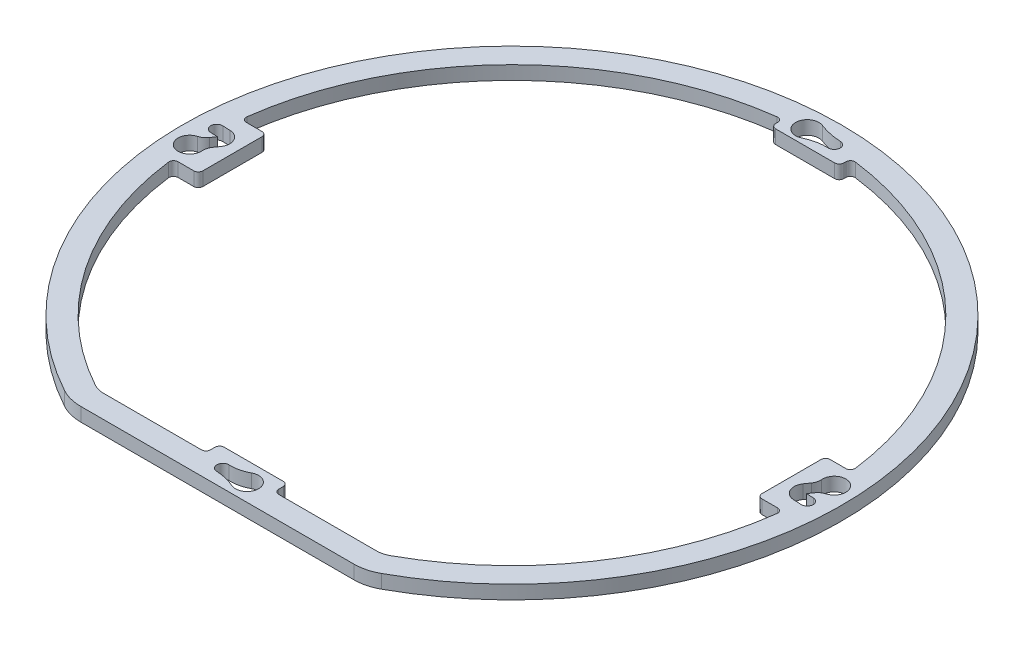
SolidWorks part; units mm, degrees
material "ABS"
ref_plane "Front Plane" through (0, 0, 0) normal (0, 0, 1) x (1, 0, 0)
ref_plane "Top Plane" through (0, 0, 0) normal (0, 1, 0) x (1, 0, 0)
ref_plane "Right Plane" through (0, 0, 0) normal (1, 0, 0) x (0, 0, -1)
sketch "Sketch1" plane through (0, 0, 0) normal (0, 1, 0) x (1, 0, 0)
  line L0 (-30.03, -64.8129) -> (30.03, -64.8129)
  line L1 (0, -85) -> (0, 0) construction
  line L2 (0, -85) -> (32.4891, -64.8129) construction
  line L3 (-30.03, -59.8129) -> (30.03, -59.8129)
  arc A0 (34.8348, -63.5829) -> (-34.8348, -63.5829) centre (0, 0) ccw
  circle A1 centre (0, -85) radius 38.25 construction
  arc A2 (30.03, -64.8129) -> (34.8348, -63.5829) centre (30.03, -54.8129) ccw
  arc A3 (-30.03, -64.8129) -> (-34.8348, -63.5829) centre (-30.03, -54.8129) cw
  arc A4 (32.4324, -59.1979) -> (-32.4324, -59.1979) centre (0, 0) ccw
  arc A5 (-30.03, -59.8129) -> (-32.4324, -59.1979) centre (-30.03, -54.8129) cw
  arc A6 (30.03, -59.8129) -> (32.4324, -59.1979) centre (30.03, -54.8129) ccw
  dimension "D1" = 145
  dimension "D2" = 76.5
  dimension "D4" = 10
  dimension "D3" = 85
  dimension "D5" = 5
extrude "Boss-Extrude1" add sketch "Sketch1" along normal blind 3
sketch "Sketch2" plane through (0, 3, 0) normal (0, 1, 0) x (1, 0, 0)
  line L0 (-30.03, -59.8129) -> (30.03, -59.8129) construction
  line L1 (7.5, -59.8129) -> (-7.5, -59.8129)
  line L2 (7.5, -59.8129) -> (7.5, -56.8129)
  line L3 (7.5, -56.8129) -> (-7.5, -56.8129)
  line L4 (-7.5, -59.8129) -> (-7.5, -56.8129)
  line L5 (-30.03, -64.8129) -> (30.03, -64.8129) construction
  line L6 (-61.5, -7.5) -> (-67.5, -7.5)
  line L7 (-61.5, -7.5) -> (-61.5, 7.5)
  line L8 (-61.5, 7.5) -> (-67.5, 7.5)
  line L9 (-67.5, -7.5) -> (-67.5, 7.5)
  line L10 (61.5, -7.5) -> (67.5, -7.5)
  line L11 (61.5, -7.5) -> (61.5, 7.5)
  line L12 (61.5, 7.5) -> (67.5, 7.5)
  line L13 (67.5, -7.5) -> (67.5, 7.5)
  line L14 (7.5, 67.5) -> (-7.5, 67.5)
  line L15 (7.5, 67.5) -> (7.5, 64.5)
  line L16 (7.5, 64.5) -> (-7.5, 64.5)
  line L17 (-7.5, 67.5) -> (-7.5, 64.5)
  arc A0 (32.4324, -59.1979) -> (-32.4324, -59.1979) centre (0, 0) ccw construction
  point P17 (-67.5, 0)
  point P18 (67.5, 0)
  point P20 (0, -56.8129)
  point P26 (0, 67.5)
  dimension "D4" = 3
  dimension "D1" = 15
  dimension "D2" = 8
  dimension "D3" = 15
  dimension "D5" = 6
extrude "Boss-Extrude2" add sketch "Sketch2" against normal up to surface (3 mm away) up to face at (0, 0, 30.3285)
sketch "Sketch3" plane through (0, 3, 0) normal (0, 1, 0) x (1, 0, 0)
  line L0 (0, 0) -> (2.6608, -60.9419) construction
  line L1 (0, 0) -> (-2.6608, -60.9419) construction
  line L2 (0, 0) -> (0, -64.8129) construction
  line L3 (-30.03, -64.8129) -> (30.03, -64.8129) construction
  line L4 (0, 0) -> (0, 72.5) construction
  line L5 (0, 0) -> (2.9661, 67.9353) construction
  line L6 (0, 0) -> (-2.9661, 67.9353) construction
  arc A0 (1.6164, -63.2683) -> (1.438, -58.7042) centre (2.6608, -60.9419) ccw
  arc A1 (-2.6041, -59.6432) -> (-2.7175, -62.2407) centre (-2.6608, -60.9419) ccw
  arc A2 (-2.6041, -59.6432) -> (1.438, -58.7042) centre (-2.2671, -51.9241) ccw
  arc A3 (1.6164, -63.2683) -> (-2.7175, -62.2407) centre (-3.2341, -74.0728) ccw
  arc A4 (34.8348, -63.5829) -> (-34.8348, -63.5829) centre (0, 0) ccw construction
  arc A5 (2.9094, 66.6365) -> (3.0228, 69.234) centre (2.9661, 67.9353) ccw
  arc A6 (-2.032, 70.308) -> (-1.8457, 65.6446) centre (-2.9661, 67.9353) ccw
  arc A7 (-2.032, 70.308) -> (3.0228, 69.234) centre (3.706, 84.8822) ccw
  arc A8 (2.9094, 66.6365) -> (-1.8457, 65.6446) centre (2.48, 56.8013) ccw
  point P23 (0, 0)
  dimension "D1" = 2.6
  dimension "D2" = 5.1
  dimension "D6" = 5.1
  dimension "D7" = 2.6
  dimension "D3" = 5
  dimension "D4" = 2.5
  dimension "D5" = 61
  dimension "D8" = 2.5
  dimension "D9" = 5
  dimension "D10" = 68
extrude "Cut-Extrude1" cut sketch "Sketch3" against normal through all
sketch "Sketch4" plane through (0, 3, 0) normal (0, 1, 0) x (1, 0, 0)
  line L0 (0, 0) -> (-72.5, 0) construction
  line L1 (0, 0) -> (-67.9353, -2.9661) construction
  line L2 (0, 0) -> (-67.9353, 2.9661) construction
  line L3 (-67.9353, -2.9661) -> (-63.9391, 2.7916) construction
  line L4 (-67.992, 1.6674) -> (-66.4106, 1.5983)
  line L5 (-67.1396, 0.548) -> (-66.4106, 1.5983)
  line L6 (-69.0443, -2.1964) -> (-65.0481, 3.5614) construction
  line L7 (-64.9215, -0.9914) -> (-64.1565, 0.1107)
  line L8 (-67.8786, 4.2649) -> (-66.1791, 4.1907)
  line L9 (67.992, -1.6674) -> (66.4106, -1.5983)
  line L10 (67.1396, -0.548) -> (66.4106, -1.5983)
  line L11 (64.9215, 0.9914) -> (64.1565, -0.1107)
  line L12 (67.8786, -4.2649) -> (66.1791, -4.1907)
  line L13 (0, 0) -> (72.5, 0) construction
  line L14 (0, 0) -> (67.9353, 2.9661) construction
  line L15 (0, 0) -> (67.9353, -2.9661) construction
  line L16 (67.9353, 2.9661) -> (63.9391, -2.7916) construction
  arc A0 (34.8348, -63.5829) -> (-34.8348, -63.5829) centre (0, 0) ccw construction
  arc A1 (-67.8786, 4.2649) -> (-67.992, 1.6674) centre (-67.9353, 2.9661) ccw
  arc A2 (-68.6262, -0.5115) -> (-65.3941, -2.7547) centre (-67.9353, -2.9661) ccw
  arc A3 (-66.1791, 4.1907) -> (-64.1565, 0.1107) centre (-66.2925, 1.5932) cw
  arc A4 (-67.1396, 0.548) -> (-68.6262, -0.5115) centre (-69.3577, 2.0875) cw
  arc A5 (-64.9215, -0.9914) -> (-65.3941, -2.7547) centre (-62.7033, -2.5309) ccw
  arc A6 (67.8786, -4.2649) -> (67.992, -1.6674) centre (67.9353, -2.9661) ccw
  arc A7 (68.6262, 0.5115) -> (65.3941, 2.7547) centre (67.9353, 2.9661) ccw
  arc A8 (66.1791, -4.1907) -> (64.1565, -0.1107) centre (66.2925, -1.5932) cw
  arc A9 (67.1396, -0.548) -> (68.6262, 0.5115) centre (69.3577, -2.0875) cw
  arc A10 (64.9215, 0.9914) -> (65.3941, 2.7547) centre (62.7033, 2.5309) ccw
  point P42 (0, 0)
  dimension "D5" = 5.1
  dimension "D6" = 2.6
  dimension "D9" = 2.7
  dimension "D1" = 68
  dimension "D2" = 5
  dimension "D3" = 2.5
  dimension "D4" = 4
  dimension "D7" = 1.35
  dimension "D8" = 1.35
  dimension "D10" = 2
extrude "Cut-Extrude2" cut sketch "Sketch4" against normal through all
fillet "Fillet1" radius 1 16 edges at (61.5, 1.5, -7.5) (67.082, 1.5, -7.5) (61.5, 1.5, 7.5) (67.082, 1.5, 7.5) (-7.5, 1.5, -64.5) (-7.5, 1.5, -67.082) (7.5, 1.5, -64.5) (7.5, 1.5, -67.082) (-67.082, 1.5, -7.5) (-61.5, 1.5, -7.5) (-61.5, 1.5, 7.5) (-67.082, 1.5, 7.5) (-7.5, 1.5, 59.8129) (-7.5, 1.5, 56.8129) (7.5, 1.5, 56.8129) (7.5, 1.5, 59.8129)
equation "\"smallPulleyTeeth\"= 30"
equation "\"largePulleyTeeth\"= 30"
equation "\"eighthThick\"= 3.0mm"
equation "\"sixteenthThick\" = 1.7mm"
equation "\"quarterThick\"=6.0mm"
equation "\"OD\" = 145mm"
equation "\"puckAngle\" = 60.5deg"
equation "\"puckDiam\" = 76.5mm"
equation "\"axlePress\" = 5.9mm"
equation "\"press\" = 0.2mm"
equation "\"wheelClear\" = 0.3mm"
equation "\"10-32clear\" = 4.8mm"
equation "\"6-32clear\" = 3.3mm"
equation "\"8-32clear\" = 4.0mm"
equation "\"4-40clear\" = 3.0mm"
equation "\"wheelHeight\" = 22mm"
equation "\"wheelWell\" = 65mm"
equation "\"D1@Sketch1\"=\"OD\""
equation "\"D1@Boss-Extrude1\"=\"eighthThick\""
equation "\"D2@Sketch1\"=\"puckDiam\""
equation "\"puckDist\" = 85mm"
equation "\"scoopFillet\" = 5mm"
equation "\"10-32tap\" = 4.45mm"
equation "\"ledSmall\" = 3.1mm"
equation "\"ledLarge\" = 4.2mm"
equation "\"ledLength\" = 4.2mm"
equation "\"D3@Sketch1\"=\"puckDist\""
